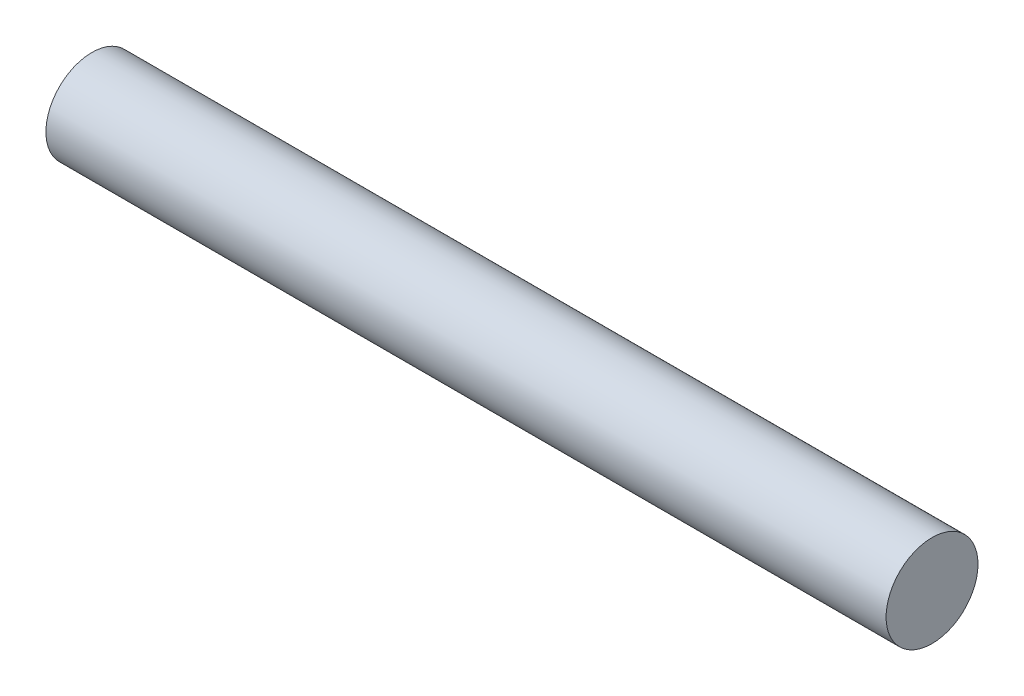
SolidWorks part; units mm, degrees
ref_plane "Front Plane" through (0, 0, 0) normal (0, 0, 1) x (1, 0, 0)
ref_plane "Top Plane" through (0, 0, 0) normal (0, 1, 0) x (1, 0, 0)
ref_plane "Right Plane" through (0, 0, 0) normal (1, 0, 0) x (0, 0, -1)
sketch "Sketch1" plane through (0, 0, 0) normal (0, 0, 1) x (1, 0, 0)
  line L0 (0, 0) -> (203.2, 0)
  line L1 (48.0728, 0) -> (-48.0728, 0) construction
  point P5 (158.75, 0)
  point P8 (44.45, 0)
  dimension "D1" = 158.75
  dimension "D2" = 44.45
  dimension "D3" = 44.45
sweep "Sweep1" add path "Sketch1" circular profile diameter 22.225 parameters "D3"=22.225
sketch "Sketch18" plane through (0, 0, 0) normal (0, 0, 1) x (1, 0, 0)
  circle A0 centre (44.45, 0) radius 3.175
  dimension "D1" = 6.35
extrude "Cut-Extrude1" cut sketch "Sketch18" against normal through all
equation "\"bar_dia\"= 0.875"
equation "\"D3@Sweep1\"=\"bar_dia\""
equation "\"hole_dia\"= 0.25in"
equation "\"D1@Sketch18\"=\"hole_dia\" "
